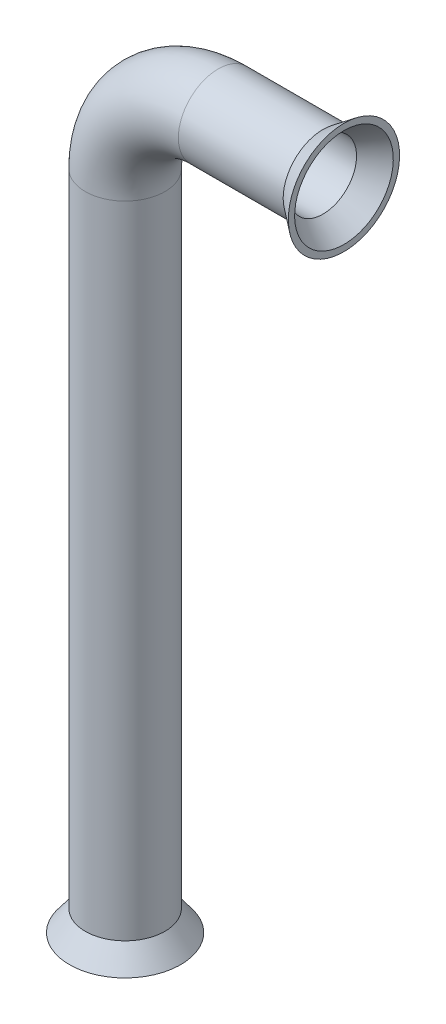
SolidWorks part; units mm, degrees
material "6061-T6 (SS)"
ref_plane "Front Plane" through (0, 0, 0) normal (0, 0, 1) x (1, 0, 0)
ref_plane "Top Plane" through (0, 0, 0) normal (0, 1, 0) x (1, 0, 0)
ref_plane "Right Plane" through (0, 0, 0) normal (1, 0, 0) x (0, 0, -1)
sketch "Sketch1" plane through (0, 0, 0) normal (0, 1, 0) x (1, 0, 0)
  circle A0 centre (0, 0) radius 4.826
  circle A1 centre (0, 0) radius 4.064
  dimension "D1" = 9.652
  dimension "D2" = 8.128
sketch "Sketch2" plane through (0, 0, 0) normal (0, 0, 1) x (1, 0, 0)
  line L0 (0, 0) -> (0, 77.6224)
  line L1 (11.2776, 88.9) -> (23.9776, 88.9)
  arc A0 (0, 77.6224) -> (11.2776, 88.9) centre (11.2776, 77.6224) cw
  point P5 (3.9611, 13.2109)
  point P7 (162.5519, 127.6097)
  point P8 (114.3, 147.9962)
  dimension "D1" = 88.9
  dimension "D2" = 12.7
  dimension "D3" = 23.9776
sweep "Sweep1" add profiles "Sketch1" path "Sketch2"
sketch "Sketch3" plane through (0, 0, 0) normal (0, -1, 0) x (1, 0, 0)
  circle A0 centre (0, 0) radius 4.826
  circle A1 centre (0, 0) radius 4.826 construction
extrude "Boss-Extrude1" add sketch "Sketch3" along normal blind 2.54 draft 37 draft outward yes
sketch "Sketch4" plane through (0, -2.54, 0) normal (0, -1, 0) x (1, 0, 0)
  line L0 (-4.826, 0) -> (-4.064, 0) construction
  line L1 (-5.978, 0) -> (-6.74, 0) construction
  circle A0 centre (0, 0) radius 5.978
  circle A1 centre (0, 0) radius 4.826 construction
  circle A2 centre (0, 0) radius 4.064 construction
  circle A3 centre (0, 0) radius 6.74 construction
  point P14 (0, 0)
extrude "Cut-Extrude1" cut sketch "Sketch4" against normal through all draft 37
sketch "Sketch5" plane through (23.9776, 0, 0) normal (1, 0, 0) x (0, 0, -1)
  circle A1 centre (0, 88.9) radius 4.826
  circle A2 centre (0, 88.9) radius 4.826 construction
  circle A3 centre (0, 88.9) radius 4.826 construction
extrude "Boss-Extrude2" add sketch "Sketch5" along normal blind 2.54 draft 37 draft outward yes
sketch "Sketch6" plane through (26.5176, 0, 0) normal (1, 0, 0) x (0, 0, -1)
  line L0 (-5.978, 88.9) -> (-6.74, 88.9) construction
  circle A0 centre (0, 88.9) radius 5.978
  circle A1 centre (0, 88.9) radius 6.74 construction
  dimension "D1" = 0.762
extrude "Cut-Extrude2" cut sketch "Sketch6" against normal through all draft 37
